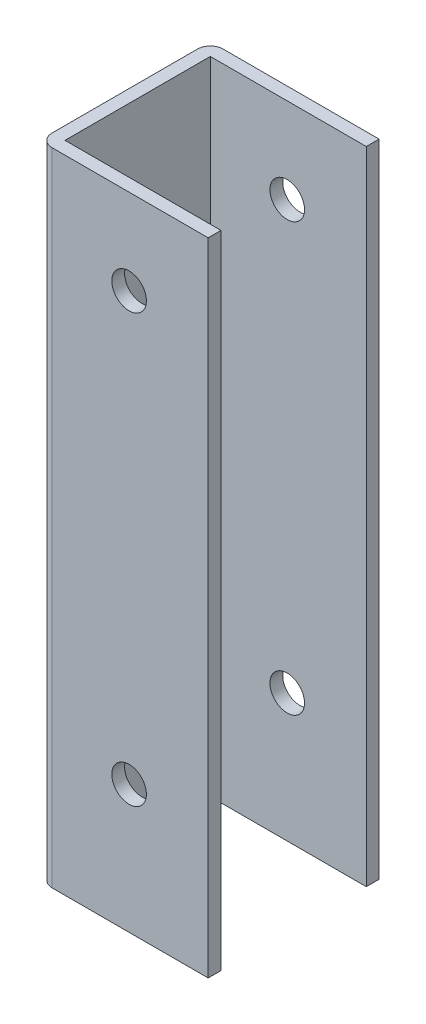
SolidWorks part; units mm, degrees
ref_plane "Спереди" through (0, 0, 0) normal (0, 0, 1) x (1, 0, 0)
ref_plane "Сверху" through (0, 0, 0) normal (0, 1, 0) x (1, 0, 0)
ref_plane "Справа" through (0, 0, 0) normal (1, 0, 0) x (0, 0, -1)
sketch "Эскиз1" plane through (0, 0, 0) normal (0, 1, 0) x (1, 0, 0)
  line L1 (-37, 20) -> (37, 20)
  line L2 (-40, 17) -> (-40, -17)
  line L3 (-37, -20) -> (37, -20)
  line L4 (40, 17) -> (40, -17)
  line L5 (-40, 20) -> (40, -20) construction
  line L6 (-40, -20) -> (40, 20) construction
  arc A0 (-37, 20) -> (-40, 17) centre (-37, 17) ccw
  arc A1 (-40, -17) -> (-37, -20) centre (-37, -17) ccw
  arc A2 (37, -20) -> (40, -17) centre (37, -17) ccw
  arc A3 (37, 20) -> (40, 17) centre (37, 17) cw
  point P0 (0, 0)
  dimension "D1" = 3
extrude "Вытянуть-Тонкостенный1" add sketch "Эскиз1" along normal blind 150 thin thin type one direction reverse wall 3
sketch "Эскиз2" plane through (0, 150, 0) normal (0, 1, 0) x (1, 0, 0)
  line L1 (-0.5, -21.5541) -> (41.1465, -21.5541)
  line L2 (-0.5, -21.5541) -> (-0.5, 20.9728)
  line L3 (-0.5, 20.9728) -> (41.1465, 20.9728)
  line L4 (41.1465, -21.5541) -> (41.1465, 20.9728)
extrude "Вырез-Вытянуть1" cut sketch "Эскиз2" against normal through all
sketch "Эскиз3" plane through (0, 0, -20) normal (0, 0, -1) x (-1, 0, 0)
  circle A0 centre (19, 130) radius 4.05
  circle A1 centre (19, 30) radius 4.05
  dimension "D1" = 2
extrude "Вырез-Вытянуть2" cut sketch "Эскиз3" against normal through all
